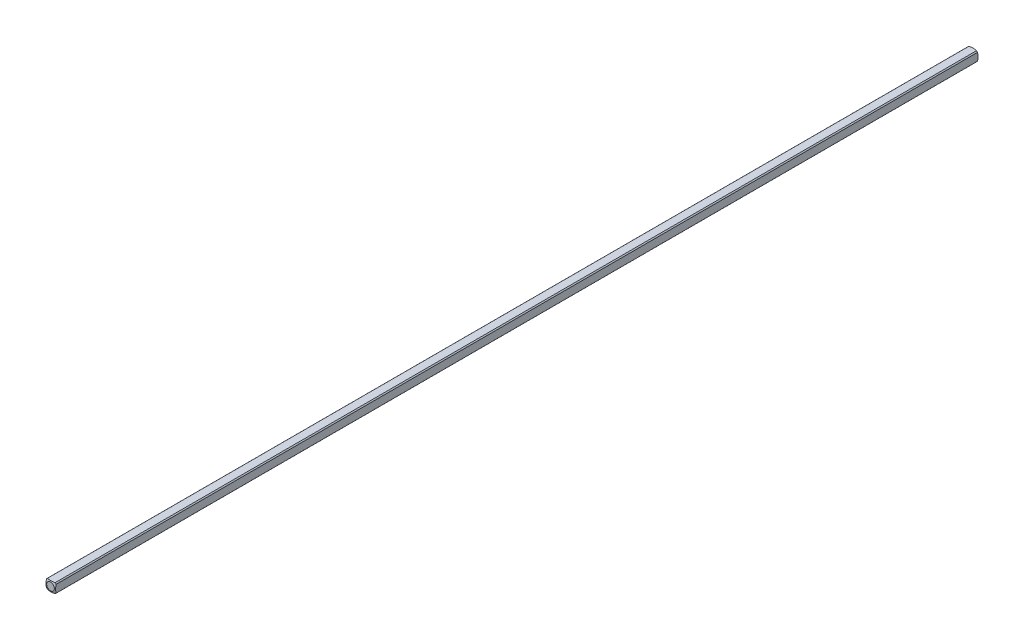
SolidWorks part; units mm, degrees
material "Custom Plastic"
ref_plane "Front Plane" through (0, 0, 0) normal (0, 0, 1) x (1, 0, 0)
ref_plane "Top Plane" through (0, 0, 0) normal (0, 1, 0) x (1, 0, 0)
ref_plane "Right Plane" through (0, 0, 0) normal (1, 0, 0) x (0, 0, -1)
sketch "Sketch1" plane through (0, 0, 0) normal (0, 0, 1) x (1, 0, 0)
  line L0 (-1.5875, -1.5875) -> (1.5875, 1.5875) construction
  line L1 (-1.5875, -1.5875) -> (1.5875, -1.5875)
  line L2 (-1.5875, -1.5875) -> (-1.5875, 1.5875)
  line L3 (-1.5875, 1.5875) -> (1.5875, 1.5875)
  line L4 (1.5875, -1.5875) -> (1.5875, 1.5875)
  dimension "D1" = 3.175
extrude "Boss-Extrude1" add sketch "Sketch1" along normal blind 152.4
sketch "Sketch2" plane through (0, 0, 0) normal (0, 0, -1) x (-1, 0, 0)
  circle A0 centre (0, 0) radius 2.032
  dimension "D1" = 4.064
extrude "Cut-Extrude1" cut sketch "Sketch2" against normal through all flip side to cut
ref_axis "Axis1" through (0, 0, 152.4) along (0, 0, -1)
sketch "Sketch3" plane through (0, 0, 0) normal (0, 1, 0) x (1, 0, 0)
  line L1 (-5.0537, -4.4027) -> (-5.0537, 5.7405)
  line L2 (-5.0537, 5.7405) -> (0, 5.7405)
  line L5 (0, -152.4) -> (0, 0) construction
  line L8 (0, 0.1609) -> (0, 5.7405)
  arc A0 (-5.0537, -4.4027) -> (0, 0.1609) centre (0, -4.9191) cw
  dimension "D1" = 5.08
revolve "Cut-Revolve1" cut sketch "Sketch3" angle 360 about axis through (0, 0, 152.4) along (0, 0, -1)
mirror "Mirror1" about plane through (0, 0, 152.4) normal (0, 0, -1) of bodies 103
